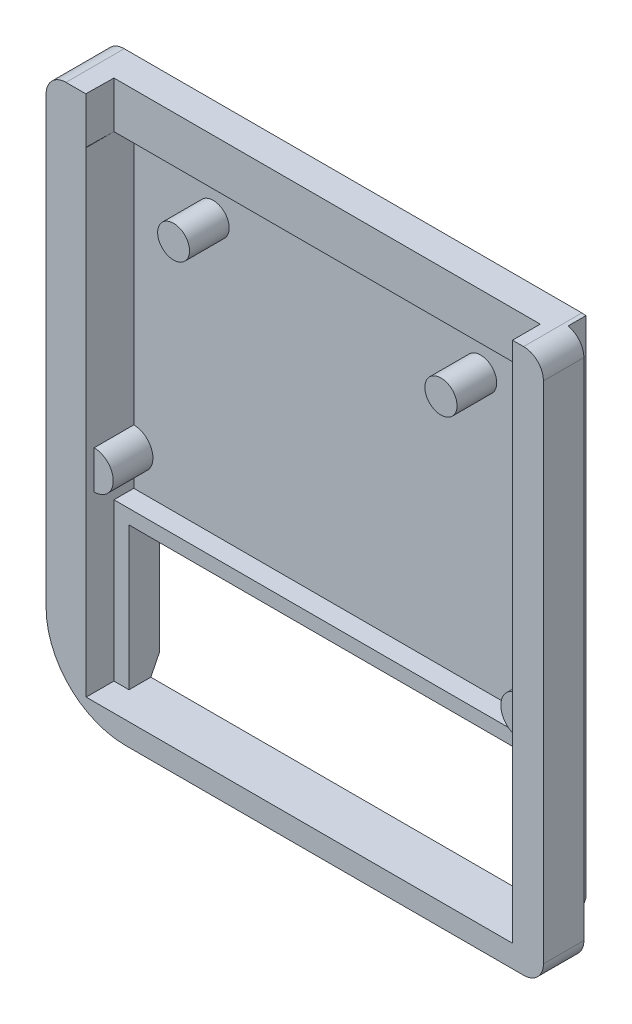
SolidWorks part; units mm, degrees
ref_plane "Front Plane" through (0, 0, 0) normal (0, 0, 1) x (1, 0, 0)
ref_plane "Top Plane" through (0, 0, 0) normal (0, 1, 0) x (1, 0, 0)
ref_plane "Right Plane" through (0, 0, 0) normal (1, 0, 0) x (0, 0, -1)
sketch "Sketch1" plane through (0, 0, -1.6) normal (0, 0, 1) x (1, 0, 0)
  circle A2 centre (138.4, -72.7) radius 1.0299 construction
  circle A3 centre (121.275, -72.675) radius 1.0213 construction
  circle A6 centre (138.4, -72.7) radius 1.0299
  circle A7 centre (121.275, -72.675) radius 1.0213
extrude "Boss-Extrude1" add sketch "Sketch1" against normal blind 1.27 and the other way blind 1.27
sketch "Sketch3" plane through (0, 0, -0.33) normal (0, 0, 1) x (1, 0, 0)
  line L32 (143.4899, -89.1669) -> (143.49, -100.2279) construction
  line L33 (143.49, -100.2279) -> (116.18, -100.2279) construction
  line L34 (116.18, -100.2279) -> (116.185, -89.1027) construction
  line L36 (143.4899, -89.1669) -> (143.49, -100.2279)
  line L37 (143.49, -100.2279) -> (116.18, -100.2279)
  line L38 (116.18, -100.2279) -> (116.185, -89.1027)
  line L39 (117.1502, -100.2279) -> (117.1502, -91.0839)
  line L40 (117.1502, -91.0839) -> (143.4899, -91.0839)
  line L41 (116.1845, -90.1695) -> (143.4899, -90.1695)
  line L42 (118.6996, -101.6503) -> (144.2012, -101.6503)
  line L44 (144.2012, -66.7761) -> (114.8896, -66.7761)
  line L45 (113.6196, -68.0461) -> (113.6196, -96.5703)
  line L46 (116.185, -89.1027) -> (116.185, -69.7479)
  line L47 (116.185, -69.7479) -> (116.2, -40.2) construction
  line L48 (116.185, -69.7479) -> (143.49, -69.7479)
  line L49 (143.5, -40.2) -> (143.49, -69.7479) construction
  line L50 (143.49, -69.7479) -> (143.4899, -89.1669)
  line L51 (145.4712, -68.0461) -> (145.4712, -100.3803)
  arc A0 (118.6996, -101.6503) -> (113.6196, -96.5703) centre (118.6996, -96.5703) cw
  arc A1 (145.4712, -68.0461) -> (144.2012, -66.7761) centre (144.2012, -68.0461) ccw
  arc A2 (114.8896, -66.7761) -> (113.6196, -68.0461) centre (114.8896, -68.0461) ccw
  arc A3 (144.2012, -101.6503) -> (145.4712, -100.3803) centre (144.2012, -100.3803) ccw
  point P22 (113.6196, -101.6503)
  point P25 (145.4712, -66.7761)
  point P30 (145.4712, -101.6503)
  dimension "D8" = 5.08
  dimension "D9" = 1.27
  dimension "D2" = 34.8742
  dimension "D1" = 2.5654
  dimension "D3" = 31.8516
  dimension "D4" = 1.4224
  dimension "D5" = 3.5306
  dimension "D6" = 9.144
  dimension "D7" = 0.9144
sketch "Sketch4" plane through (0, 0, -2.87) normal (0, 0, 1) x (1, 0, 0)
  line L0 (113.6196, -68.0461) -> (113.6196, -96.5703) construction
  line L5 (118.6996, -101.6503) -> (144.2012, -101.6503) construction
  line L6 (145.4712, -68.0461) -> (145.4712, -100.3803) construction
  line L7 (144.2012, -66.7761) -> (114.8896, -66.7761) construction
  line L8 (113.6196, -68.0461) -> (113.6196, -96.5703)
  line L9 (118.6996, -101.6503) -> (144.2012, -101.6503)
  line L10 (145.4712, -68.0461) -> (145.4712, -100.3803)
  line L11 (144.2012, -66.7761) -> (114.8896, -66.7761)
  line L13 (117.1502, -91.0839) -> (143.49, -91.0839)
  line L14 (117.1502, -91.0839) -> (117.1502, -100.2279)
  line L15 (117.1502, -100.2279) -> (143.49, -100.2279)
  line L16 (143.49, -91.0839) -> (143.49, -100.2279)
  arc A0 (113.6196, -96.5703) -> (118.6996, -101.6503) centre (118.6996, -96.5703) ccw construction
  arc A1 (144.2012, -101.6503) -> (145.4712, -100.3803) centre (144.2012, -100.3803) ccw construction
  arc A2 (145.4712, -68.0461) -> (144.2012, -66.7761) centre (144.2012, -68.0461) ccw construction
  arc A3 (114.8896, -66.7761) -> (113.6196, -68.0461) centre (114.8896, -68.0461) ccw construction
  arc A4 (113.6196, -96.5703) -> (118.6996, -101.6503) centre (118.6996, -96.5703) ccw
  arc A5 (144.2012, -101.6503) -> (145.4712, -100.3803) centre (144.2012, -100.3803) ccw
  arc A6 (145.4712, -68.0461) -> (144.2012, -66.7761) centre (144.2012, -68.0461) ccw
  arc A7 (114.8896, -66.7761) -> (113.6196, -68.0461) centre (114.8896, -68.0461) ccw
extrude "Boss-Extrude2" add sketch "Sketch4" against normal blind 0.6858
sketch "Sketch7" plane through (0, 0, -2.87) normal (0, 0, 1) x (1, 0, 0)
  line L0 (113.6196, -68.0461) -> (113.6196, -96.5703) construction
  line L1 (116.185, -69.7479) -> (143.49, -69.7479)
  line L2 (116.185, -69.7479) -> (116.185, -100.2279)
  line L3 (116.185, -100.2279) -> (143.49, -100.2279)
  line L4 (143.49, -69.7479) -> (143.49, -100.2279)
  line L5 (118.6996, -101.6503) -> (144.2012, -101.6503) construction
  line L6 (145.4712, -68.0461) -> (145.4712, -100.3803) construction
  line L7 (144.2012, -66.7761) -> (114.8896, -66.7761) construction
  line L8 (113.6196, -68.0461) -> (113.6196, -96.5703)
  line L9 (118.6996, -101.6503) -> (144.2012, -101.6503)
  line L10 (145.4712, -68.0461) -> (145.4712, -100.3803)
  line L11 (144.2012, -66.7761) -> (114.8896, -66.7761)
  arc A0 (113.6196, -96.5703) -> (118.6996, -101.6503) centre (118.6996, -96.5703) ccw construction
  arc A1 (144.2012, -101.6503) -> (145.4712, -100.3803) centre (144.2012, -100.3803) ccw construction
  arc A2 (145.4712, -68.0461) -> (144.2012, -66.7761) centre (144.2012, -68.0461) ccw construction
  arc A3 (114.8896, -66.7761) -> (113.6196, -68.0461) centre (114.8896, -68.0461) ccw construction
  arc A4 (113.6196, -96.5703) -> (118.6996, -101.6503) centre (118.6996, -96.5703) ccw
  arc A5 (144.2012, -101.6503) -> (145.4712, -100.3803) centre (144.2012, -100.3803) ccw
  arc A6 (145.4712, -68.0461) -> (144.2012, -66.7761) centre (144.2012, -68.0461) ccw
  arc A7 (114.8896, -66.7761) -> (113.6196, -68.0461) centre (114.8896, -68.0461) ccw
extrude "Boss-Extrude10" add sketch "Sketch7" along normal blind 3.048
sketch "Sketch8" plane through (0, 0, -2.87) normal (0, 0, 1) x (1, 0, 0)
  line L0 (116.185, -89.1027) -> (116.185, -86.6528)
  line L1 (116.185, -89.1027) -> (116.185, -69.7479) construction
  line L2 (143.4899, -89.1669) -> (143.4899, -86.6528)
  line L3 (143.49, -69.7479) -> (143.4899, -89.1669) construction
  arc A0 (116.185, -86.6528) -> (116.185, -89.1027) centre (116.185, -87.8777) cw
  arc A1 (143.4899, -89.1669) -> (143.4899, -86.6528) centre (143.4899, -87.9098) cw
  line M1 (116.185, -69.7479) -> (116.185, -100.2279)
  dimension "D1" = 2.4499
extrude "Boss-Extrude11" add sketch "Sketch8" along normal blind 2.54 contours A0 M1 | A1 L2 region at (116.7049, -87.8777, -2.87) region at (142.9564, -87.9098, -2.87)
sketch "Sketch10" plane through (0, 0, -2.87) normal (0, 0, 1) x (1, 0, 0)
  line L0 (116.1845, -90.1695) -> (143.4899, -90.1695)
  line L1 (143.4899, -90.1695) -> (143.4899, -91.0839)
  line L2 (143.4899, -91.0839) -> (117.1502, -91.0839)
  line L3 (117.1502, -91.0839) -> (117.1502, -100.2279)
  line L4 (117.1502, -100.2279) -> (116.185, -100.2279)
  line L5 (116.185, -100.2279) -> (116.1845, -90.1695)
extrude "Boss-Extrude12" add sketch "Sketch10" along normal blind 1.27
sketch "Sketch11" plane through (145.4712, 0, 0) normal (1, 0, 0) x (0, 0, -1)
  line L0 (3.5558, -101.6503) -> (-0.178, -101.6503) construction
  line L1 (3.5558, -66.7761) -> (2.4128, -66.7761)
  line L2 (3.5558, -66.7761) -> (3.5558, -101.6503)
  line L3 (3.5558, -101.6503) -> (2.4128, -101.6503)
  line L4 (2.4128, -66.7761) -> (2.4128, -101.6503)
  line L5 (-0.178, -100.3803) -> (-0.178, -68.0461) construction
  dimension "D1" = 2.5908
extrude "Cut-Extrude2" cut sketch "Sketch11" against normal blind 1.016
sketch "Sketch12" plane through (0, -69.7479, 0) normal (0, -1, 0) x (1, 0, 0)
  line L0 (143.4899, -1.6) -> (116.185, -1.6) construction
  line L1 (143.4899, -1.6) -> (116.185, -1.6)
  line L2 (116.185, -1.6) -> (116.1596, 0.178)
  line L3 (118.6996, 0.178) -> (113.6196, 0.178) construction
  line L4 (116.1596, 0.178) -> (143.4899, 0.178)
  line L5 (118.6996, 0.178) -> (144.2012, 0.178) construction
  line L6 (143.4899, 0.178) -> (143.4899, -1.6)
extrude "Cut-Extrude3" cut sketch "Sketch12" against normal up to next
sketch "Sketch13" plane through (145.4712, 0, 0) normal (1, 0, 0) x (0, 0, -1)
  line L0 (3.5558, -101.6503) -> (2.2858, -101.6503)
  line L1 (3.5558, -101.6503) -> (-0.178, -101.6503) construction
  line L2 (2.2858, -101.6503) -> (3.5558, -99.1103)
  line L3 (3.5558, -66.8018) -> (3.5558, -101.6246) construction
  line L4 (3.5558, -99.1103) -> (3.5558, -101.6503)
  dimension "D1" = 2.54
  dimension "D2" = 1.27
extrude "Cut-Extrude4" cut sketch "Sketch13" against normal up to surface (31.8516 mm away) up to face at (113.6196, -82.3082, -1.6889)
sketch "Sketch14" plane through (113.6196, 0, 0) normal (-1, 0, 0) x (0, 0, 1)
  line L0 (-3.5558, -68.0461) -> (-3.5558, -96.5703) construction
  line L1 (-3.5558, -95.6559) -> (-1.473, -95.6559)
  line L2 (-3.5558, -95.6559) -> (-3.5558, -101.6503)
  line L3 (-3.5558, -101.6503) -> (-1.473, -101.6503)
  line L4 (-1.473, -95.6559) -> (-1.473, -101.6503)
  line L5 (-2.2858, -101.6503) -> (0.178, -101.6503) construction
  dimension "D1" = 2.0828
  dimension "D2" = 5.9944
extrude "Cut-Extrude5" cut sketch "Sketch14" against normal blind 1.397
sketch "Sketch15" plane through (113.6196, 0, 0) normal (-1, 0, 0) x (0, 0, 1)
  line L0 (-3.5558, -68.0461) -> (-3.5558, -95.6559) construction
  line L1 (-3.5558, -88.1629) -> (-1.7778, -88.1629)
  line L2 (-3.5558, -88.1629) -> (-3.5558, -85.3181)
  line L3 (-3.5558, -85.3181) -> (-1.7778, -85.3181)
  line L4 (-1.7778, -88.1629) -> (-1.7778, -85.3181)
  line L5 (-3.5558, -66.7761) -> (0.178, -66.7761) construction
  dimension "D1" = 18.542
  dimension "D2" = 1.778
  dimension "D3" = 2.8448
extrude "Cut-Extrude6" cut sketch "Sketch15" against normal blind 1.4986
